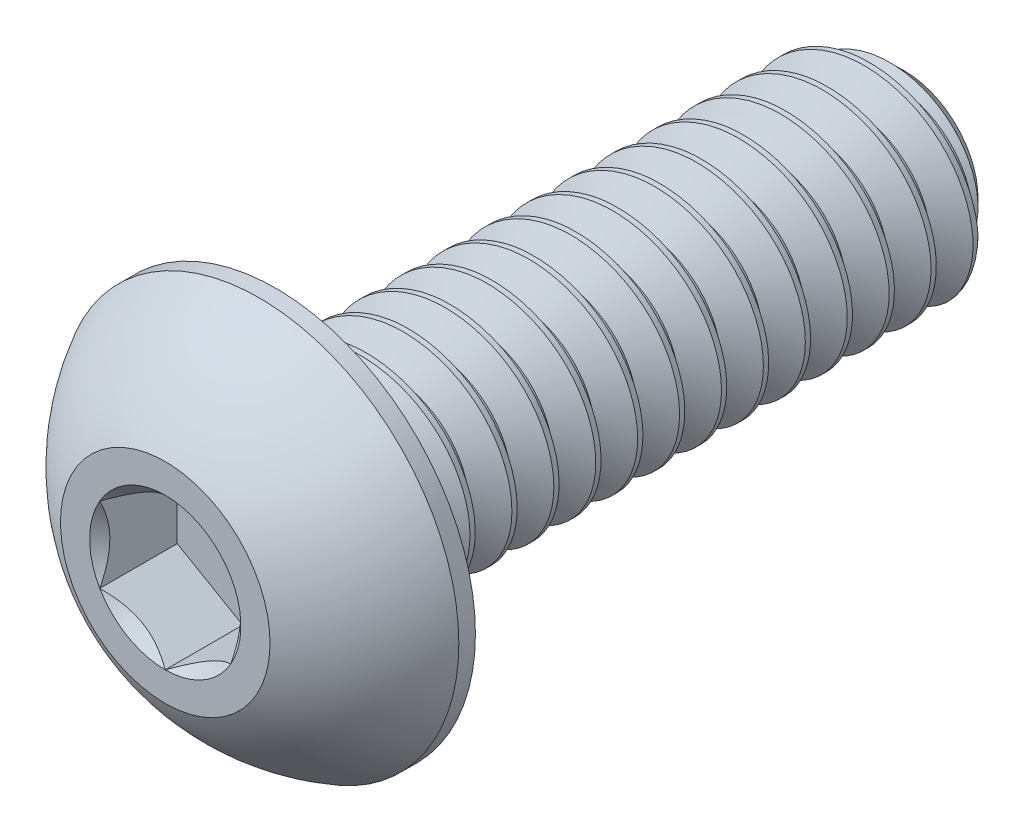
SolidWorks part; units mm, degrees
material "AISI 304"
ref_plane "Front" through (0, 0, 0) normal (0, 0, 1) x (1, 0, 0)
ref_plane "Top" through (0, 0, 0) normal (0, 1, 0) x (1, 0, 0)
ref_plane "Right" through (0, 0, 0) normal (1, 0, 0) x (0, 0, -1)
sketch "Sketch1" plane through (0, 0, 0) normal (1, 0, 0) x (0, 0, -1)
  line L2 (1.6764, 1.5875) -> (11.2014, 1.5875)
  line L3 (11.2014, 1.5875) -> (11.2014, 0)
  line L4 (11.2014, 0) -> (1.6764, 0)
  line L6 (1.4249, 3.0226) -> (1.6764, 3.0226) construction
  line L7 (11.2014, 1.5875) -> (11.2014, -1.5875) construction
  line L8 (0, 0) -> (1.6764, 0) construction
  line L9 (1.6764, 3.0226) -> (1.6764, -3.0226) construction
  line L11 (1.6764, 1.5875) -> (1.6764, 0)
  line L13 (0, 0.9922) -> (0, -0.9922) construction
  line L14 (0, 0.9922) -> (0, 1.5875) construction
  arc A3 (0, 1.5875) -> (1.4249, 3.0226) centre (3.034, 0) cw construction
  dimension "D1" = 0.2515
revolve "Revolve1" add sketch "Sketch1" angle 360 mid plane about L4
sketch "Sketch3" plane through (0, 0, -11.2014) normal (0, 0, -1) x (-1, 0, 0)
  circle A0 centre (0, 0) radius 1.5875
curve "Helix/Spiral1" pitch 0.635 height 10.16 radius 1.5875 centre (0, 0, -11.2014) axis (0, 0, 1) start towards (0, 1, 0)
sketch "Sketch2" plane through (0, 0, 0) normal (1, 0, 0) x (0, 0, -1)
  line L0 (11.2014, 1.5875) -> (11.757, 1.5875)
  line L1 (11.757, 1.5875) -> (11.5189, 1.1751)
  line L2 (11.5189, 1.1751) -> (11.4395, 1.1751)
  line L3 (11.4395, 1.1751) -> (11.2014, 1.5875)
  line L4 (11.3205, 1.3813) -> (11.638, 1.3813) construction
  dimension "D1" = 60
  dimension "D2" = 0.0794
  dimension "D3" = 0.3175
chamfer "Chamfer1" distance 0.4763 angle 45 1 edges at (0, 1.5875, -11.2014)
sweep "Cut-Sweep1" cut profiles "Sketch2" path "Helix/Spiral1" align with end faces yes
sketch "Sketch7" plane through (0, 0, 0) normal (1, 0, 0) x (0, 0, -1)
  line L6 (1.4249, 3.0226) -> (1.6764, 3.0226) construction
  line L8 (0, 0) -> (1.6764, 0) construction
  line L11 (1.6764, 3.0226) -> (1.6764, -3.0226) construction
  line L12 (1.4249, 3.0226) -> (1.6764, 3.0226)
  line L13 (0, 0) -> (1.6764, 0)
  line L14 (0, 0.9922) -> (0, -0.9922) construction
  line L15 (1.6764, 3.0226) -> (1.6764, 0)
  line L16 (0, 1.5875) -> (0, 0)
  arc A2 (1.4249, 3.0226) -> (0, 1.5875) centre (3.034, 0) ccw construction
  arc A3 (1.4249, 3.0226) -> (0, 1.5875) centre (3.034, 0) ccw
revolve "Revolve2" add sketch "Sketch7" angle 360 mid plane about L13
sketch "Sketch5" plane through (0, 0, 0) normal (0, 0, 1) x (1, 0, 0)
  line L1 (0.9922, -0.5728) -> (0.9922, 0.5728)
  line L2 (0.9922, 0.5728) -> (0, 1.1457)
  line L3 (0, 1.1457) -> (-0.9922, 0.5728)
  line L4 (-0.9922, 0.5728) -> (-0.9922, -0.5728)
  line L5 (-0.9922, -0.5728) -> (0, -1.1457)
  line L6 (0, -1.1457) -> (0.9922, -0.5728)
  circle A0 centre (0, 0) radius 0.9922 construction
extrude "Cut-Extrude2" cut sketch "Sketch5" against normal blind 1.1735
sketch "Sketch6" plane through (0, 0, 0) normal (0, 0, 1) x (1, 0, 0)
  circle A0 centre (0, 0) radius 1.1457
extrude "Cut-Extrude3" cut sketch "Sketch6" against normal blind 1.1735 draft 45
sketch "Sketch9" [suppressed] plane through (0, 0, -1.4986) normal (0, 0, 1) x (1, 0, 0)
  circle A2 centre (0, 0) radius 1.4224
extrude "Boss-Extrude2" [suppressed] add sketch "Sketch9" against normal offset from surface (12.7 mm away) 31.75 up to face at (0, 1.1113, -11.2014)
sketch "Sketch10" plane through (0, 0, 0) normal (1, 0, 0) x (0, 0, -1)
  line L0 (11.2014, 1.5875) -> (11.2014, -1.5875) construction
  point P0 (10.2489, -1.5875)
  dimension "D1" = 0.9525
equation "\"D3@Helix/Spiral1\" = \"Lg@Sketch1\" + \"D4@Helix/Spiral1\""
equation "\"D2@Sketch2\" = \"D4@Helix/Spiral1\" * .125"
equation "\"D3@Sketch2\" = \"D4@Helix/Spiral1\" * .5"
equation "\"D1@Chamfer1\" = \"D4@Helix/Spiral1\" * .75"
equation "\"D1@Cut-Extrude2\" = \"Head Ht@Sketch1\" * .7"
equation "\"D1@Sketch1\" = \"Head Ht@Sketch1\" * .15"
equation "\"D1@Sketch10\" = \"D4@Helix/Spiral1\" * 1.5"
equation "\"D1@Cut-Extrude3\" = \"D1@Cut-Extrude2\""
